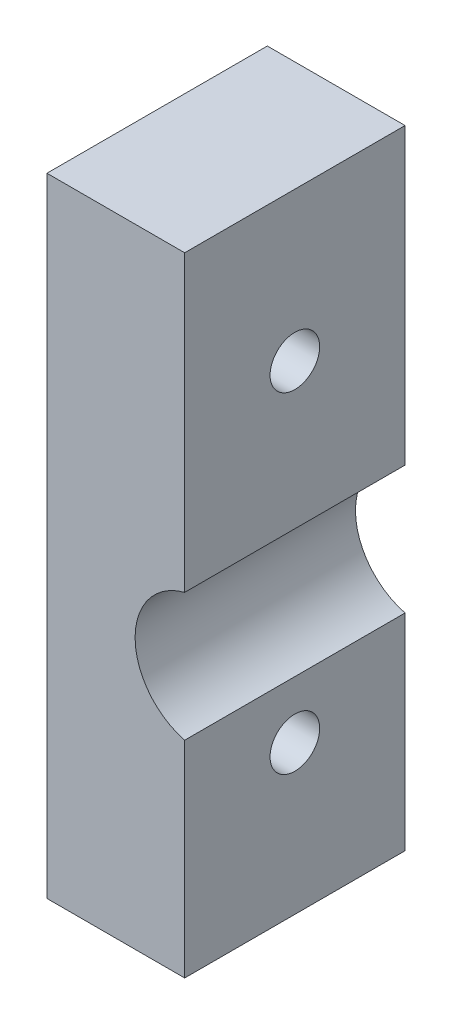
SolidWorks part; units mm, degrees
material "3D printed plastic"
ref_plane "Front Plane" through (0, 0, 0) normal (0, 0, 1) x (1, 0, 0)
ref_plane "Top Plane" through (0, 0, 0) normal (0, 1, 0) x (1, 0, 0)
ref_plane "Right Plane" through (0, 0, 0) normal (1, 0, 0) x (0, 0, -1)
sketch "Sketch1" plane through (0, 0, 0) normal (0, 0, 1) x (1, 0, 0)
  line L0 (0, 0) -> (15, 0) construction
  line L1 (-14, 32.5) -> (-1.5, 32.5)
  line L2 (-14, 32.5) -> (-14, -24.5)
  line L3 (-14, -24.5) -> (-1.5, -24.5)
  line L4 (15, 33.5) -> (15, 23)
  line L5 (1.5, -25.5) -> (15, -25.5)
  line L6 (1.5, -5.8095) -> (1.5, -25.5)
  line L7 (-1.5, 32.5) -> (-1.5, 5.8095)
  line L8 (15, -15) -> (15, -25.5)
  line L9 (1.5, 33.5) -> (1.5, 5.8095)
  line L10 (1.5, 33.5) -> (15, 33.5)
  line L11 (-1.5, -5.8095) -> (-1.5, -24.5)
  line L12 (-1.5, 5.8095) -> (1.5, 5.8095) construction
  line L13 (15, 23) -> (15.6, 23)
  line L14 (15.6, 19) -> (15, 19) construction
  line L15 (15, 15) -> (15.6, 15)
  line L16 (15.6, 23) -> (15.6, 15)
  line L17 (15, -7) -> (15.6, -7)
  line L18 (15, 15) -> (15, -7)
  line L19 (15, -15) -> (15.6, -15)
  line L20 (15.6, -7) -> (15.6, -15)
  line L21 (15.6, -11) -> (16.2538, -11) construction
  arc A0 (1.5, -5.8095) -> (1.5, 5.8095) centre (0, 0) ccw
  arc A1 (-1.5, 5.8095) -> (-1.5, -5.8095) centre (0, 0) ccw
  dimension "D1" = 59
  dimension "D2" = 12
  dimension "D3" = 15
  dimension "D4" = 29
  dimension "D5" = 3
  dimension "D6" = 8
  dimension "D7" = 30
  dimension "D8" = 0.6
  dimension "D9" = 25.5
  dimension "D10" = 1
  dimension "D11" = 1
extrude "Boss-Extrude1" add sketch "Sketch1" along normal mid plane 20
hole_wizard "CBORE for M5 Hex Socket Head Cap Screw1" positions "Sketch3" profile "Sketch2" counterbore size "M5" standard "DIN" end condition through all
sketch "Sketch3" plane through (-14, 0, 0) normal (-1, 0, 0) x (0, 0, 1)
  line L0 (0, 19) -> (0, -11) construction
  line L2 (0, 4) -> (-10, 4) construction
  line L3 (-10, 32.5) -> (-10, -24.5) construction
  line L5 (0, 4) -> (10, 4) construction
  line L7 (10, 32.5) -> (10, -24.5) construction
  point P0 (0, -11)
  point P2 (0, 19)
  dimension "D1" = 30
sketch "Sketch2" plane through (-14, -11, 0) normal (0, 1, 0) x (0, 0, 1)
  line L0 (0, 0) -> (0, 29.6)
  line L1 (0, 29.6) -> (2.25, 29.6)
  line L3 (2.25, 29.6) -> (2.25, 5.9)
  line L4 (2.25, 5.9) -> (5, 5.9)
  line L5 (5, 5.9) -> (5, 0)
  line L7 (5, 0) -> (0, 0)
  line L11 (0, -6.35) -> (0, 107.95) construction
  dimension "Thru Hole Dia." = 4.5
  dimension "Thru Hole Depth" = 29.6
  dimension "C'Bore Dia." = 10
  dimension "C'Bore Depth" = 5.9
sketch "Sketch4" plane through (0, 0, 10) normal (0, 0, 1) x (1, 0, 0)
  line L0 (1.5, 5.8095) -> (1.5, -5.8095)
  line L13 (15, -25.5) -> (15, -15)
  line L14 (15, -15) -> (15.6, -15)
  line L15 (15.6, -15) -> (15.6, -7)
  line L16 (15.6, -7) -> (15, -7)
  line L17 (15, -7) -> (15, 15)
  line L18 (15, 15) -> (15.6, 15)
  line L19 (15.6, 15) -> (15.6, 23)
  line L20 (15.6, 23) -> (15, 23)
  line L21 (15, 23) -> (15, 33.5)
  line L22 (15, 33.5) -> (1.5, 33.5)
  line L23 (1.5, 33.5) -> (1.5, 5.8095)
  line L24 (1.5, -5.8095) -> (1.5, -25.5)
  line L25 (1.5, -25.5) -> (15, -25.5)
  line L26 (15, -25.5) -> (15, -15)
  line L27 (15, -15) -> (15.6, -15)
  line L28 (15.6, -15) -> (15.6, -7)
  line L29 (15.6, -7) -> (15, -7)
  line L30 (15, -7) -> (15, 15)
  line L31 (15, 15) -> (15.6, 15)
  line L32 (15.6, 15) -> (15.6, 23)
  line L33 (15.6, 23) -> (15, 23)
  line L34 (15, 23) -> (15, 33.5)
  line L35 (15, 33.5) -> (1.5, 33.5)
  line L36 (1.5, 33.5) -> (1.5, 5.8095)
  line L37 (1.5, -5.8095) -> (1.5, -25.5)
  line L38 (1.5, -25.5) -> (15, -25.5)
  arc A1 (1.5, -5.8095) -> (1.5, 5.8095) centre (0, 0) ccw
  dimension "D1" = 0
extrude "Boss-Extrude2" add sketch "Sketch4" along normal blind 13
sketch "Sketch5" plane through (0, 0, -10) normal (0, 0, -1) x (-1, 0, 0)
  line L0 (-15, -25.5) -> (-1.5, -25.5)
  line L1 (-15, -15) -> (-15, -25.5)
  line L2 (-15.6, -7) -> (-15, -7)
  line L3 (-15.6, -7) -> (-15.6, -15)
  line L4 (-15.6, -15) -> (-15, -15)
  line L5 (-1.5, 5.8095) -> (-1.5, 33.5)
  line L13 (-15, -15) -> (-15, -25.5)
  line L14 (-15, -25.5) -> (-1.5, -25.5)
  line L15 (-1.5, -25.5) -> (-1.5, -5.8095)
  line L16 (-1.5, 5.8095) -> (-1.5, 33.5)
  line L17 (-1.5, 33.5) -> (-15, 33.5)
  line L18 (-15, 33.5) -> (-15, 23)
  line L19 (-15, 23) -> (-15.6, 23)
  line L20 (-15.6, 23) -> (-15.6, 15)
  line L21 (-15.6, 15) -> (-15, 15)
  line L22 (-15, 15) -> (-15, -7)
  line L23 (-15, -7) -> (-15.6, -7)
  line L24 (-15.6, -7) -> (-15.6, -15)
  line L25 (-15.6, -15) -> (-15, -15)
  line L29 (-1.5, -25.5) -> (-1.5, -5.8095)
  line L30 (-1.5, 33.5) -> (-15, 33.5)
  line L31 (-15, 33.5) -> (-15, 23)
  line L32 (-15, 23) -> (-15.6, 23)
  line L33 (-15.6, 23) -> (-15.6, 15)
  line L34 (-15.6, 15) -> (-15, 15)
  line L35 (-15, 15) -> (-15, -7)
  arc A0 (-1.5, 5.8095) -> (-1.5, -5.8095) centre (0, 0) ccw
  arc A1 (-1.5, 5.8095) -> (-1.5, -5.8095) centre (0, 0) ccw
  dimension "D1" = 0
extrude "Boss-Extrude3" add sketch "Sketch5" along normal blind 23
sketch "Sketch7" plane through (0, 33.5, 0) normal (0, 1, 0) x (1, 0, 0)
  line L0 (1.5, 33) -> (-4.9, 33)
  line L1 (-4.9, 33) -> (-4.9, 17.4)
  line L2 (-4.9, 17.4) -> (1.5, 11)
  line L3 (1.5, -23) -> (1.5, 33) construction
  line L4 (1.5, 11) -> (1.5, 33)
  dimension "D1" = 6.4
  dimension "D2" = 45
  dimension "D3" = 11
extrude "Boss-Extrude4" add sketch "Sketch7" against normal blind 27
sketch "Sketch8" plane through (-4.9, 0, 0) normal (-1, 0, 0) x (0, 0, 1)
  line L0 (-33, 33.5) -> (-17.4, 33.5) construction
  line L1 (-33, 6.5) -> (-33, 33.5) construction
  circle A0 centre (-25, 19) radius 2.1
  dimension "D1" = 14.5
  dimension "D2" = 8
  dimension "D3" = 4.2
extrude "Cut-Extrude1" cut sketch "Sketch8" against normal through all
chamfer "Chamfer1" distance 16 angle 45 1 edges at (8.25, -25.5, -33)
sketch "Sketch9" plane through (15.6, 0, 0) normal (1, 0, 0) x (0, 0, -1)
  line L1 (29.0992, 19) -> (27.0496, 22.55)
  line L2 (27.0496, 22.55) -> (22.9504, 22.55)
  line L3 (22.9504, 22.55) -> (20.9008, 19)
  line L4 (20.9008, 19) -> (22.9504, 15.45)
  line L5 (22.9504, 15.45) -> (27.0496, 15.45)
  line L6 (27.0496, 15.45) -> (29.0992, 19)
  circle A0 centre (25, 19) radius 3.55 construction
  dimension "D1" = 7.1
extrude "Cut-Extrude2" cut sketch "Sketch9" against normal blind 6
sketch "Sketch10" plane through (-4.9, 0, 0) normal (-1, 0, 0) x (0, 0, 1)
  circle A0 centre (-25, 19) radius 5
  circle A1 centre (-25, 19) radius 2.1
  circle A2 centre (-25, 19) radius 2.1 construction
  dimension "D1" = 10
extrude "Boss-Extrude5" add sketch "Sketch10" along normal blind 0.7
chamfer "Chamfer2" distance 1 angle 45 1 edges at (-5.6, 19, -20)
delete or keep bodies "Body-Delete1" type delete bodies bodies 110
